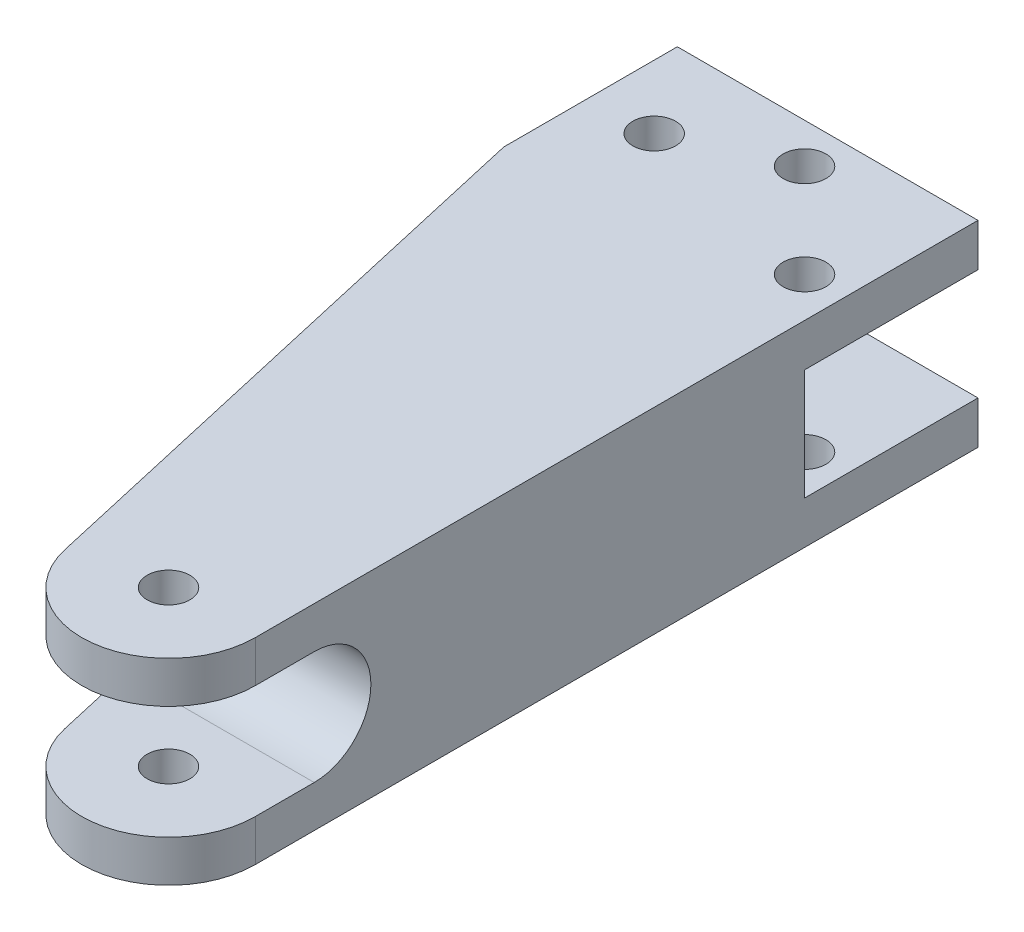
SolidWorks part; units mm, degrees
material "2024-T3"
ref_plane "Front Plane" through (0, 0, 0) normal (0, 0, 1) x (1, 0, 0)
ref_plane "Top Plane" through (0, 0, 0) normal (0, 1, 0) x (1, 0, 0)
ref_plane "Right Plane" through (0, 0, 0) normal (1, 0, 0) x (0, 0, -1)
sketch "Sketch1" plane through (0, 0, 0) normal (0, 0, 1) x (1, 0, 0)
  line L0 (-9.525, -10.795) -> (9.525, -10.795)
  line L1 (-9.525, -10.795) -> (-9.525, 10.795)
  line L2 (9.525, -10.795) -> (9.525, 10.795)
  line L3 (-9.525, 10.795) -> (9.525, 10.795)
  line L4 (-9.525, -10.795) -> (9.525, 10.795) construction
  line L5 (9.525, -10.795) -> (-9.525, 10.795) construction
  point P1 (0, 0)
  dimension "D1" = 21.59
  dimension "D2" = 19.05
extrude "Boss-Extrude1" add sketch "Sketch1" along normal blind 88.9
sketch "Sketch3" plane through (0, 10.795, 0) normal (0, 1, 0) x (1, 0, 0)
  line L0 (-9.525, -88.9) -> (-9.525, 0) construction
  line L1 (9.525, -88.9) -> (9.525, 0) construction
  line L2 (9.525, -88.9) -> (-9.525, -88.9) construction
  arc A0 (-9.525, -79.375) -> (9.525, -79.375) centre (0, -79.375) ccw
extrude "Cut-Extrude-Thin1" cut sketch "Sketch3" against normal blind 88.9 and the other way through all thin thin type one direction wall 25.4
sketch "Sketch4" plane through (0, 10.795, 0) normal (0, 1, 0) x (1, 0, 0)
  line L0 (5.1435, -14.6685) -> (9.525, -14.6685) construction
  line L1 (9.525, -79.375) -> (9.525, 0) construction
  line L2 (-9.525, 0) -> (9.525, -19.05) construction
  line L3 (-5.1435, -4.3815) -> (-5.1435, 0) construction
  line L4 (-9.525, 0) -> (9.525, 0) construction
  line L5 (-9.525, 0) -> (-9.525, -19.05) construction
  line L6 (-9.525, -19.05) -> (9.525, -19.05) construction
  line L7 (9.525, 0) -> (9.525, -19.05) construction
  circle A0 centre (0, -79.375) radius 2.3495
  circle A1 centre (5.1435, -14.6685) radius 2.3495
  circle A2 centre (-5.1435, -4.3815) radius 2.3495
  dimension "D1" = 4.699
  dimension "D2" = 4.3815
  dimension "D3" = 4.3815
extrude "Cut-Extrude1" cut sketch "Sketch4" against normal through all
sketch "Sketch5" plane through (0, 10.795, 0) normal (0, 1, 0) x (1, 0, 0)
  line L0 (-9.525, 0) -> (-23.495, 0)
  line L1 (-23.495, 0) -> (-23.495, -19.05)
  line L2 (-9.525, -79.375) -> (-9.525, 0) construction
  line L3 (-9.525, -79.375) -> (-9.525, 0)
  line L4 (-23.495, -19.05) -> (-9.2876, -81.4883)
  arc A0 (-9.525, -79.375) -> (9.525, -79.375) centre (0, -79.375) ccw construction
  arc A1 (-9.525, -79.375) -> (9.525, -79.375) centre (0, -79.375) ccw
  circle A2 centre (-16.51, -9.525) radius 2.3495
  circle A3 centre (-5.1435, -4.3815) radius 2.3495 construction
  point P14 (-16.51, 0)
  point P17 (-23.495, -9.525)
  line M9 (-9.525, 0) -> (-9.525, -79.375)
  arc M10 (-9.525, -79.375) -> (9.525, -79.375) centre (0, -79.375) ccw
  dimension "D1" = 13.97
  dimension "D2" = 19.05
  dimension "D3" = 12.819
extrude "Boss-Extrude2" add sketch "Sketch5" against normal up to surface (21.59 mm away) contours L1 L4 L0 A2 M10 M9 region at (-15.0361, 10.795, 28.5077) up to face at (0, -10.795, 81.7245)
sketch "Sketch6" plane through (9.525, 0, 0) normal (1, 0, 0) x (0, 0, -1)
  line L0 (19.05, -6.096) -> (19.05, 6.096)
  line L1 (19.05, -6.096) -> (-19.05, -6.096)
  line L2 (19.05, 6.096) -> (-19.05, 6.096)
  line L3 (-19.05, -6.096) -> (-19.05, 6.096)
  line L4 (19.05, -6.096) -> (-19.05, 6.096) construction
  line L5 (19.05, 6.096) -> (-19.05, -6.096) construction
  line L6 (-92.075, -6.223) -> (-72.898, -6.223)
  line L7 (-92.075, -6.223) -> (-92.075, 6.223)
  line L9 (-92.075, 6.223) -> (-72.898, 6.223)
  line L10 (-92.075, -6.223) -> (-69.1843, 4.9934) construction
  line L11 (-69.1843, -4.9934) -> (-92.075, 6.223) construction
  line L12 (-79.375, -10.795) -> (-79.375, 10.795) construction
  line L13 (-79.375, -10.795) -> (-79.375, 10.795) construction
  arc A0 (-72.898, 6.223) -> (-72.898, -6.223) centre (-72.898, 0) cw
  point P1 (0, 0)
  point P2 (-79.375, 0)
  point P14 (-79.375, 0)
  dimension "D1" = 12.192
  dimension "D2" = 19.05
extrude "Cut-Extrude2" cut sketch "Sketch6" against normal through all
ref_plane "Plane1" through (0, 0, 0) normal (0, 1, 0) x (1, 0, 0)
ref_axis "Axis1" through (0, 6.223, 79.375) along (0, 1, 0)
ref_point "Point4"
move or copy body "Body-Move/Copy1" [suppressed] bodies to move or copy 105
